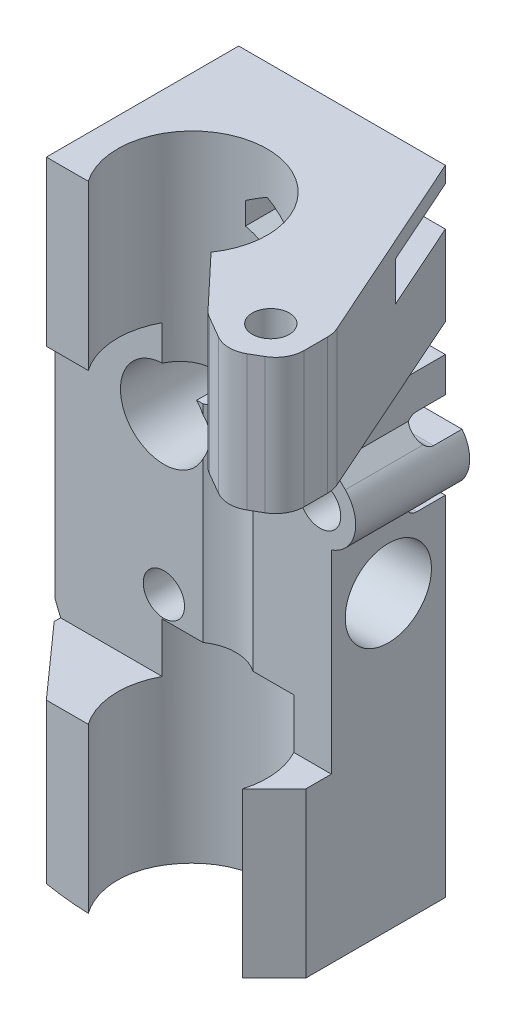
SolidWorks part; units mm, degrees
material "ABS"
ref_plane "Front Plane" through (0, 0, 0) normal (0, 0, 1) x (1, 0, 0)
ref_plane "Top Plane" through (0, 0, 0) normal (0, 1, 0) x (1, 0, 0)
ref_plane "Right Plane" through (0, 0, 0) normal (1, 0, 0) x (0, 0, -1)
sketch "Sketch1" plane through (0, 0, 0) normal (0, 0, 1) x (1, 0, 0)
  line L0 (-26, 0) -> (29.6968, 0) construction
  line L1 (16.5, -28) -> (23.5, -35) construction
  line L2 (-5.5, 34) -> (-26, 3.5)
  line L3 (25.4558, 3.5355) -> (23.5, 5.4914)
  line L4 (21.9203, -5) -> (16.5, -5) construction
  line L5 (23.5, 34) -> (-5.5, 34)
  line L6 (21.9203, 0) -> (0, 21.9203) construction
  line L7 (0, 21.9203) -> (-21.9203, 0) construction
  line L8 (-21.9203, 0) -> (0, -21.9203) construction
  line L9 (0, -21.9203) -> (21.9203, 0) construction
  line L10 (23.5, -35) -> (23.5, -55)
  line L11 (16.5, -5) -> (16.5, -28) construction
  line L12 (-26, 3.5) -> (-26, -3.5)
  line L13 (-5.5, -54.3205) -> (-26, -3.5)
  line L14 (23.5, -35) -> (23.5, -4.7439)
  line L18 (9, 25) -> (9, -47) construction
  line L20 (1.5, 26.9068) -> (1.5, -55) construction
  line L21 (1.5, -55) -> (23.5, -55)
  line L22 (23.5, 34) -> (23.5, 5.4914)
  arc A0 (23.5, -4.7439) -> (25.4558, 3.5355) centre (21.9203, 0) ccw
  circle A1 centre (0, 0) radius 15.5 construction
  circle A2 centre (0, 21.9203) radius 1.55 construction
  circle A3 centre (21.9203, 0) radius 1.55
  circle A4 centre (0, -21.9203) radius 1.55
  circle A5 centre (-21.9203, 0) radius 1.55
  circle A6 centre (0, 0) radius 5.5 construction
  circle A7 centre (9, 25) radius 1.55
  circle A8 centre (0, 0) radius 6.1
  arc A9 (-5.5, -54.3205) -> (1.5, -55) centre (1.5, -18.6027) ccw
  circle A10 centre (9, -47) radius 1.55
  point P18 (26.8692, -2.8293)
  point P19 (26.8692, 2.8293)
  dimension "D2" = 31
  dimension "D3" = 3.1
  dimension "D4" = 11
  dimension "D12" = 12.2
  dimension "D7" = 10
  dimension "D17" = 9
  dimension "D18" = 8
  dimension "D11" = 26
  dimension "D8" = 20
  dimension "D9" = 29
  dimension "D5" = 16.5
  dimension "D6" = 23.5
  dimension "D10" = 7
  dimension "D13" = 55
  dimension "D14" = 34
  dimension "D15" = 1.5
  dimension "D16" = 9
extrude "Boss-Extrude1" add sketch "Sketch1" along normal blind 27
sketch "Sketch2" plane through (0, 0, 0) normal (1, 0, 0) x (0, 0, -1)
  circle A0 centre (-8, -14) radius 6.05
  dimension "D1" = 12.1
  dimension "D3" = 14
  dimension "D2" = 8
extrude "Cut-Extrude1" cut sketch "Sketch2" along normal through all and the other way blind 15
sketch "Sketch3" plane through (0, 0, 0) normal (0, 1, 0) x (1, 0, 0)
  circle A0 centre (9, -21) radius 6.1
  dimension "D1" = 12.2
  dimension "D3" = 21
  dimension "D2" = 9
extrude "Cut-Extrude4" cut sketch "Sketch3" against normal through all and the other way through all
sketch "Sketch7" plane through (0, 0, 0) normal (1, 0, 0) x (0, 0, -1)
  line L0 (-2, -14) -> (-2, 0) construction
  line L1 (-3.0927, 0) -> (-12.9856, 0) construction
  line L2 (-4, 4.6) -> (0, 4.6) construction
  line L3 (-4, 6.1) -> (0, 6.1)
  line L4 (-4, 3.1) -> (0, 3.1)
  line L5 (-4, -4.6) -> (0, -4.6) construction
  line L6 (-4, -6.1) -> (0, -6.1)
  line L7 (-4, -3.1) -> (0, -3.1)
  line L8 (-2, -14) -> (-8, -14) construction
  line L9 (0, 3.5355) -> (0, 5.4914) construction
  arc A0 (-4, 6.1) -> (-4, 3.1) centre (-4, 4.6) ccw
  arc A1 (0, 3.1) -> (0, 6.1) centre (0, 4.6) ccw
  arc A2 (-4, -6.1) -> (-4, -3.1) centre (-4, -4.6) cw
  arc A3 (0, -3.1) -> (0, -6.1) centre (0, -4.6) cw
  circle A4 centre (-8, -14) radius 6.05 construction
  point P8 (-2, 4.6)
  point P15 (-2, -4.6)
  dimension "D2" = 1.5
  dimension "D1" = 4.6
  dimension "D3" = 4
extrude "Cut-Extrude12" cut sketch "Sketch7" along normal through all
sketch "Sketch4" plane through (0, 0, 27) normal (0, 0, 1) x (1, 0, 0)
  line L1 (-32.1475, 11) -> (31.8484, 11)
  line L2 (-40.5002, 29.7437) -> (-40.5002, -51.4715) construction
  line L3 (-32.1475, -32) -> (31.8484, -32)
  line L4 (31.8484, 11) -> (31.8484, -32)
  line L5 (10.1, -55) -> (23.5, -55) construction
  line L7 (-5.5, 29.7437) -> (-40.5002, 29.7437) construction
  line L8 (23.5, 34) -> (10.1, 34) construction
  line L9 (-5.5, -51.4715) -> (-40.5002, -51.4715) construction
  line L11 (-32.1475, 11) -> (-32.1475, -32)
  point P6 (16.8, -55)
  dimension "D1" = 23
  dimension "D2" = 23
extrude "Cut-Extrude6" cut sketch "Sketch4" against normal offset from surface (11 mm away) 16 up to face at (10.55, 25, 0)
sketch "Sketch5" plane through (0, -55, 0) normal (0, -1, 0) x (1, 0, 0)
  circle A0 centre (9, 21) radius 10.5
  arc A1 (7.9, 27) -> (10.1, 27) centre (9, 21) ccw construction
  dimension "D1" = 21
extrude "Cut-Extrude7" cut sketch "Sketch5" against normal blind 30
sketch "Sketch6" plane through (0, 34, 0) normal (0, 1, 0) x (1, 0, 0)
  circle A0 centre (9, -21) radius 10.5
  arc A1 (10.1, -27) -> (7.9, -27) centre (9, -21) ccw construction
  arc A2 (17.6168, -27) -> (1.5, -13.6515) centre (9, -21) ccw construction
extrude "Cut-Extrude11" cut sketch "Sketch6" against normal blind 30
sketch "Sketch8" plane through (0, 0, 0) normal (0, 1, 0) x (1, 0, 0)
  line L0 (-5.5, -27) -> (-26, -4)
  line L1 (-26, -16) -> (-26, 0) construction
  line L2 (-26, -4) -> (-26, -27)
  line L3 (-26, -27) -> (-5.5, -27)
  line L4 (-5.5, -27) -> (-20.959, -27) construction
  dimension "D1" = 5.5
  dimension "D2" = 4
extrude "Cut-Extrude13" cut sketch "Sketch8" against normal through all and the other way through all
sketch "Sketch9" plane through (0, 0, 0) normal (0, 0, 1) x (1, 0, 0)
  circle A0 centre (-21.9203, 0) radius 2.9
  circle A1 centre (-21.9203, 0) radius 1.55 construction
  circle A2 centre (21.9203, 0) radius 2.9
  circle A3 centre (21.9203, 0) radius 1.55 construction
  circle A4 centre (0, -21.9203) radius 2.9
  circle A5 centre (0, -21.9203) radius 1.55 construction
  dimension "D1" = 5.8
extrude "Cut-Extrude14" cut sketch "Sketch9" along normal through all from offset 5.3
sketch "Sketch10" plane through (0, 0, 16) normal (0, 0, 1) x (1, 0, 0)
  line L1 (0, -6.1) -> (30.4815, -6.1)
  line L4 (30.4815, -6.1) -> (30.4815, 6.1)
  line L5 (0, -6.1) -> (0, 6.1)
  line L6 (0, 6.1) -> (30.4815, 6.1)
  dimension "D1" = 12.2
extrude "Cut-Extrude15" [suppressed] cut sketch "Sketch10" against normal offset from surface (8 mm away) 8
sketch "Sketch11" plane through (0, 0, 0) normal (0, 0, 1) x (1, 0, 0)
  line L1 (11.7, 23.4412) -> (11.7, 26.5588)
  line L2 (11.7, 26.5588) -> (9, 28.1177)
  line L3 (9, 28.1177) -> (6.3, 26.5588)
  line L4 (6.3, 26.5588) -> (6.3, 23.4412)
  line L5 (6.3, 23.4412) -> (9, 21.8823)
  line L6 (9, 21.8823) -> (11.7, 23.4412)
  line L7 (9, -50.1177) -> (11.7, -48.5588)
  line L8 (11.7, -48.5588) -> (11.7, -45.4412)
  line L9 (11.7, -45.4412) -> (9, -43.8823)
  line L10 (9, -43.8823) -> (6.3, -45.4412)
  line L11 (6.3, -45.4412) -> (6.3, -48.5588)
  line L12 (6.3, -48.5588) -> (9, -50.1177)
  circle A0 centre (9, 25) radius 2.7 construction
  circle A1 centre (9, -47) radius 2.7 construction
  circle A2 centre (9, -47) radius 1.55 construction
  circle A3 centre (9, 25) radius 1.55 construction
  dimension "D1" = 5.4
extrude "Cut-Extrude16" cut sketch "Sketch11" along normal through all from offset 5
sketch "Sketch12" plane through (-15, 0, 0) normal (1, 0, 0) x (0, 0, -1)
  circle A0 centre (-8, -14) radius 1.55
  circle A1 centre (-8, -14) radius 6.05 construction
  dimension "D1" = 3.1
extrude "Cut-Extrude17" [suppressed] cut sketch "Sketch12" against normal through all
sketch "Sketch13" [suppressed] plane through (-15, 0, 0) normal (1, 0, 0) x (0, 0, -1)
  line L0 (-4.85, -14) -> (-4.85, -58.8173)
  line L1 (-4.85, -58.8173) -> (-11.15, -58.8173)
  line L2 (-11.15, -58.8173) -> (-11.15, -14)
  arc A0 (-4.85, -14) -> (-11.15, -14) centre (-8, -14) ccw
  circle A1 centre (-8, -14) radius 1.55 construction
  dimension "D1" = 6.3
extrude "Cut-Extrude18" [suppressed] cut sketch "Sketch13" against normal through all from offset 5 offset against normal yes
sketch "Sketch15" plane through (23.5, 0, 0) normal (1, 0, 0) x (0, 0, -1)
  line L0 (0, 6.1) -> (0, 34) construction
  line L1 (0, 11) -> (-8, 11)
  line L2 (0, 11) -> (0, 14.5295)
  line L6 (0, 15) -> (-8, 15)
  line L7 (0, 15) -> (0, 14.5295)
  line L9 (-8, 15) -> (-8, 11)
  dimension "D1" = 4
  dimension "D2" = 11
  dimension "D4" = 8
extrude "Cut-Extrude20" cut sketch "Sketch15" against normal blind 6
chamfer "Chamfer1" distance 8 angle 45 1 edges at (17.5, 13, 8) tangent propagation no
sketch "Sketch16" plane through (0, -55, 0) normal (0, -1, 0) x (1, 0, 0)
  line L0 (19.0623, 24) -> (23.5, 19.5623)
  line L1 (23.5, 27) -> (23.5, 0) construction
  line L2 (23.5, 19.5623) -> (23.5, 27)
  line L3 (23.5, 27) -> (17.6168, 27)
  line L4 (17.6168, 27) -> (19.0623, 24)
  arc A1 (1.5, 13.6515) -> (17.6168, 27) centre (9, 21) ccw construction
  dimension "D2" = 3
  dimension "D1" = 45
extrude "Cut-Extrude21" cut sketch "Sketch16" against normal up to surface (23 mm away) up to face at (-7.1832, -32, 20.5971)
sketch "Sketch17" plane through (0, 34, 0) normal (0, 1, 0) x (1, 0, 0)
  line L0 (23.5, 0) -> (36.1, -28.2668)
  line L1 (25.8433, 0) -> (5.2536, 0) construction
  line L2 (23.5, -27) -> (23.5, 0) construction
  line L4 (17.6168, -27) -> (24.9, -34.7332)
  line L5 (17.6168, -27) -> (23.5, -27)
  line L6 (23.5, -27) -> (23.5, 0)
  line L7 (36.1, -28.2668) -> (30.5, -25.0337) construction
  line L8 (30.5, -25.0337) -> (24.9, -28.2668) construction
  line L9 (24.9, -28.2668) -> (24.9, -34.7332) construction
  line L10 (24.9, -34.7332) -> (30.5, -37.9663)
  line L11 (30.5, -37.9663) -> (36.1, -34.7332)
  line L12 (36.1, -34.7332) -> (36.1, -28.2668)
  circle A0 centre (30.5, -31.5) radius 2.6
  circle A2 centre (30.5, -31.5) radius 5.6 construction
  dimension "D1" = 5.2
  dimension "D2" = 3
  dimension "D3" = 7
  dimension "D4" = 31.5
extrude "Boss-Extrude2" add sketch "Sketch17" against normal up to surface (19 mm away) up to face at (21.5, 15, 2)
sketch "Sketch18" plane through (0, 15, 0) normal (0, -1, 0) x (1, 0, 0)
  line L1 (34.5, 29.1906) -> (34.5, 33.8094)
  line L2 (34.5, 33.8094) -> (30.5, 36.1188)
  line L3 (30.5, 36.1188) -> (26.5, 33.8094)
  line L4 (26.5, 33.8094) -> (26.5, 29.1906)
  line L5 (26.5, 29.1906) -> (30.5, 26.8812)
  line L6 (30.5, 26.8812) -> (34.5, 29.1906)
  circle A0 centre (30.5, 31.5) radius 4 construction
  dimension "D1" = 8
extrude "Cut-Extrude22" cut sketch "Sketch18" against normal blind 4
fillet "Fillet1" radius 4 4 edges at (24.9, 24.5, 34.7332) (30.5, 24.5, 37.9663) (36.1, 24.5, 34.7332) (36.1, 24.5, 28.2668)
sketch "Sketch19" plane through (0, 0, 0) normal (0, 0, -1) x (-1, 0, 0)
  line L0 (-23.5, 34) -> (5.5, 34) construction
  line L1 (-20.4123, 31.75) -> (-28.5253, 31.75)
  line L2 (-23.5877, 31.75) -> (-25.1754, 29) construction
  line L3 (-25.1754, 29) -> (-23.5877, 26.25) construction
  line L4 (-28.5253, 26.25) -> (-20.4123, 26.25)
  line L5 (-20.4123, 26.25) -> (-18.8246, 29)
  line L6 (-18.8246, 29) -> (-20.4123, 31.75)
  line L7 (-28.5253, 31.75) -> (-30.113, 29)
  line L8 (-30.113, 29) -> (-28.5253, 26.25)
  circle A0 centre (-22, 29) radius 2.75 construction
  dimension "D1" = 5.5
  dimension "D2" = 5
  dimension "D3" = 22
extrude "Cut-Extrude23" cut sketch "Sketch19" against normal blind 4
chamfer "Chamfer2" distance 4.8 angle 45 1 edges at (25.283, 29, 4) first distance on face at (22.043, 29, 4)
